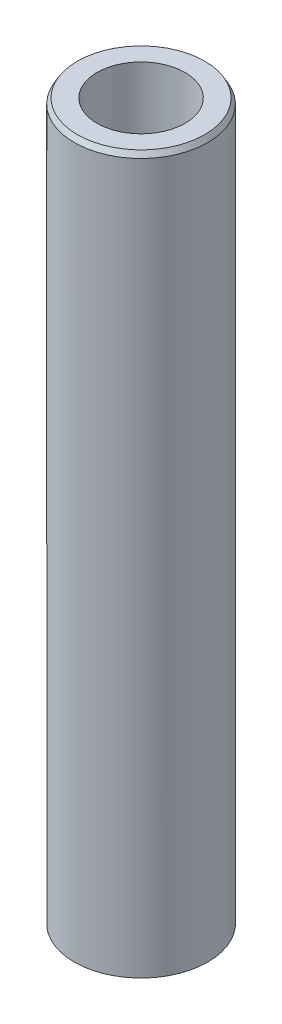
SolidWorks part; units mm, degrees
ref_plane "Front Plane" through (0, 0, 0) normal (0, 0, 1) x (1, 0, 0)
ref_plane "Top Plane" through (0, 0, 0) normal (0, 1, 0) x (1, 0, 0)
ref_plane "Right Plane" through (0, 0, 0) normal (1, 0, 0) x (0, 0, -1)
sketch "Sketch1" plane through (0, 0, 0) normal (0, 1, 0) x (1, 0, 0)
  circle A0 centre (0, 0) radius 40
  dimension "SHAFT_OD" = 80
extrude "Boss-Extrude1" add sketch "Sketch1" along normal blind 430.3827
sketch "Sketch2" plane through (0, 0, 0) normal (0, 1, 0) x (1, 0, 0)
  circle A0 centre (0, 0) radius 26.3971
  dimension "BORE_D" = 52.7942
extrude "Cut-Extrude1" cut sketch "Sketch2" along normal through all
chamfer "Chamfer1" distance 3.1856 angle 30 2 edges at (0, 430.3827, 40) (0, 0, 40) first distance on face at (0, 430.3827, 40) first distance on face at (0, 0, 26.3971)
